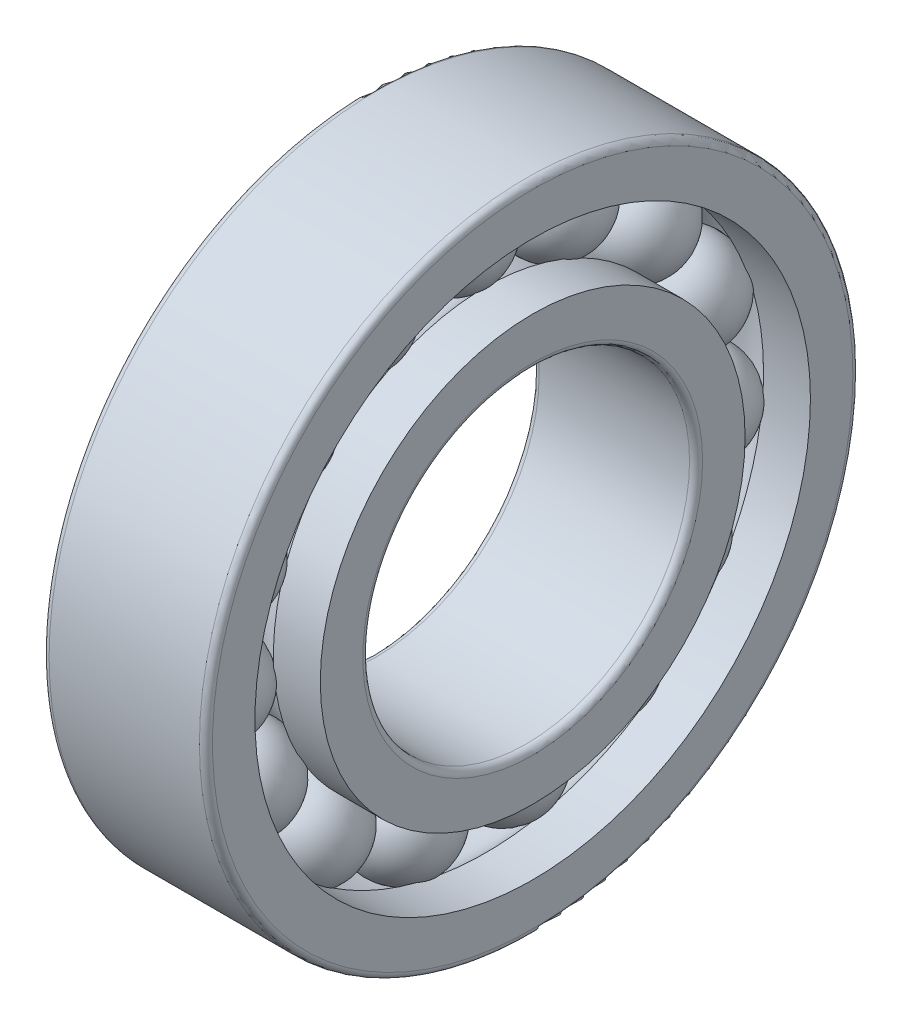
SolidWorks part; units mm, degrees
ref_plane "Plane1" through (0, 0, 0) normal (0, 0, 1) x (1, 0, 0)
ref_plane "Plane2" through (0, 0, 0) normal (0, 1, 0) x (1, 0, 0)
ref_plane "Plane3" through (0, 0, 0) normal (1, 0, 0) x (0, 0, -1)
other "Configuration Table"
sketch "Clipboard" plane through (0, 0, 0) normal (0, 0, 1) x (1, 0, 0)
  line L0 (-10, 0) -> (10, 0) construction
  line L1 (0, 0) -> (21.5988, -5.7874)
  line L2 (0, 0) -> (4.7618, -0.0831)
  line L3 (0, 0) -> (22.3573, 0.3902)
  line L4 (0, 0) -> (-22.3573, -0.3902)
sketch "CagSpiSke" plane through (0, 0, 0) normal (0, 0, 1) x (1, 0, 0)
  line L0 (0.0952, 4.6038) -> (0.0953, 4.9213)
  line L1 (0.0953, 4.9213) -> (-0.0953, 4.9213)
  line L2 (-0.0953, 4.9213) -> (-0.0952, 4.6038)
  line L3 (-0.0952, 4.6038) -> (0.0952, 4.6038)
  line L4 (-20.6375, 0) -> (20.6375, 0) construction
  line L5 (0, 0) -> (0, 23.7692) construction
revolve "CageSpine" add sketch "CagSpiSke" angle 0.001 about L4 reverse direction yes
ref_axis "Axis1" through (-50, 0, 0) along (1, 0, 0)
sketch "CagBalSke" plane through (0, 0, 0) normal (0, 0, 1) x (1, 0, 0)
  line L0 (-1.0478, 4.7625) -> (1.0478, 4.7625)
  line L1 (-1.905, 4.7625) -> (1.905, 4.7625) construction
  line L2 (-10, 0) -> (10, 0) construction
  line L3 (0, 0) -> (0, 24) construction
  arc A0 (1.0478, 4.7625) -> (-1.0478, 4.7625) centre (0, 4.7625) cw
revolve "CageBall" [suppressed] add sketch "CagBalSke" angle 360 about L1 reverse direction yes
pattern_circular "CageBalls" [suppressed] count 15 every 24 about axis through (-50, 0, 0) along (1, 0, 0)
sketch "CagTrmODSke" plane through (0, 0, 0) normal (0, 0, 1) x (1, 0, 0)
  line L0 (1.0488, 4.9212) -> (1.0488, 5.8113)
  line L1 (1.0488, 5.8113) -> (-1.0488, 5.8113)
  line L2 (-1.0488, 5.8113) -> (-1.0488, 4.9212)
  line L3 (-1.0488, 4.9212) -> (1.0488, 4.9212)
  line L4 (-20.6375, 0) -> (20.6375, 0) construction
  line L5 (0, 0) -> (0, 25) construction
revolve "CageTrimOD" [suppressed] cut sketch "CagTrmODSke" angle 360 about L4 reverse direction yes
sketch "CagTrmIDSke" plane through (0, 0, 0) normal (0, 0, 1) x (1, 0, 0)
  line L0 (1.0487, 3.7158) -> (1.0488, 4.6037)
  line L1 (1.0488, 4.6037) -> (-1.0488, 4.6037)
  line L2 (-1.0488, 4.6037) -> (-1.0487, 3.7158)
  line L3 (-1.0487, 3.7158) -> (1.0487, 3.7158)
  line L4 (-20.6375, 0) -> (20.6375, 0) construction
  line L5 (0, 0) -> (0, 25) construction
revolve "CageTrimID" [suppressed] cut sketch "CagTrmIDSke" angle 360 about L4 reverse direction yes
sketch "BalSimSke" plane through (0, 0, 0) normal (0, 0, 1) x (1, 0, 0)
  line L0 (-10, 0) -> (10, 0) construction
  line L1 (-10, 4.7625) -> (10, 4.7625) construction
  line L2 (0, 0) -> (0, 23) construction
  circle A0 centre (0, 4.7625) radius 0.9525
revolve "BallsSimplified" [suppressed] add sketch "BalSimSke" angle 360 about L0
sketch "BalDetSke" plane through (0, 0, 0) normal (0, 0, 1) x (1, 0, 0)
  line L0 (-0.9525, 4.7625) -> (0.9525, 4.7625)
  line L1 (-1.905, 4.7625) -> (1.905, 4.7625) construction
  line L2 (0, 0) -> (0, 25) construction
  arc A0 (0.9525, 4.7625) -> (-0.9525, 4.7625) centre (0, 4.7625) cw
revolve "BallDetailed" add sketch "BalDetSke" angle 360 about L1 reverse direction yes
sketch "InnRacSke" plane through (0, 0, 0) normal (0, 0, 1) x (1, 0, 0)
  line L0 (-0.676, 4.1275) -> (-1.5875, 4.1275)
  line L1 (-1.5875, 4.1275) -> (-1.5875, 3.302)
  line L2 (-1.4605, 3.175) -> (1.4605, 3.175)
  line L3 (1.5875, 3.302) -> (1.5875, 4.1275)
  line L4 (1.5875, 4.1275) -> (0.676, 4.1275)
  line L5 (-20.6375, 0) -> (20.6375, 0) construction
  line L6 (0, 0) -> (0, 30) construction
  arc A0 (-1.5875, 3.302) -> (-1.4605, 3.175) centre (-1.4605, 3.302) ccw
  arc A1 (1.4605, 3.175) -> (1.5875, 3.302) centre (1.4605, 3.302) ccw
  arc A2 (0.676, 4.1275) -> (-0.676, 4.1275) centre (0, 4.7625) cw
  dimension "OD" = 8.255
revolve "InnerRace" add sketch "InnRacSke" angle 360 about L5 reverse direction yes
sketch "OutRacSke" plane through (0, 0, 0) normal (0, 0, 1) x (1, 0, 0)
  line L0 (-0.676, 5.3975) -> (-1.5875, 5.3975)
  line L1 (-1.5875, 5.3975) -> (-1.5875, 6.223)
  line L2 (-1.4605, 6.35) -> (1.4605, 6.35)
  line L3 (1.5875, 6.223) -> (1.5875, 5.3975)
  line L4 (1.5875, 5.3975) -> (0.676, 5.3975)
  line L5 (-20.6375, 0) -> (20.6375, 0) construction
  line L6 (0, 0) -> (0, 30) construction
  arc A0 (-1.5875, 6.223) -> (-1.4605, 6.35) centre (-1.4605, 6.223) cw
  arc A1 (1.4605, 6.35) -> (1.5875, 6.223) centre (1.4605, 6.223) cw
  arc A2 (0.676, 5.3975) -> (-0.676, 5.3975) centre (0, 4.7625) ccw
revolve "OuterRace" add sketch "OutRacSke" angle 360 about L5 reverse direction yes
pattern_circular "BallsDetailed" count 15 every 24 about axis through (-50, 0, 0) along (1, 0, 0) of "BallDetailed"
equation "\"BallCLRad@Clipboard\" = ( \"OD@OutRacSke\" + \"ID@InnRacSke\" ) / 4"
equation "\"BallCLRad@BalSimSke\" = \"BallCLRad@Clipboard\""
equation "\"BallCLRad@BalDetSke\" = \"BallCLRad@Clipboard\""
equation "\"BallCLRad@InnRacSke\" = \"BallCLRad@Clipboard\""
equation "\"BallCLRad@OutRacSke\" = \"BallCLRad@Clipboard\""
equation "\"Ball_diameter@InnRacSke\" = \"Ball_diameter@BalDetSke\" - 0.05"
equation "\"Ball_diameter@OutRacSke\" = \"Ball_diameter@BalDetSke\" - 0.05"
equation "\"Ball_diameter@BalSimSke\" = \"Ball_diameter@BalDetSke\""
equation "\"Width@OutRacSke\" = \"Width@InnRacSke\""
equation "\"Fillet_radius@OutRacSke\" = \"Fillet_radius@InnRacSke\""
equation "\"Max_count@Clipboard\" = int( 3.14159265 / atn(( \"Ball_diameter@BalDetSke\" / 2) / sqr( \"BallCLRad@Clipboard\"  *  \"BallCLRad@Clipboard\" - ( \"Ball_diameter@BalDetSke\" / 2) *  ( \"Ball_diameter@BalDetSke\" / 2))))"
equation "\"Max_count@Clipboard\" = ((sgn( \"Max_count@Clipboard\" - \"Count@Clipboard\" )-1)*( \"Max_count@Clipboard\" - \"Count@Clipboard\" ))/-2+ \"Count@Clipboard\""
equation "\"Count@BallsDetailed\" = int( \"Show_count@Clipboard\" ) "
equation "\"Count@BallsDetailed\" = ((sgn( \"Count@BallsDetailed\" - \"Max_count@Clipboard\" )-1)*( \"Count@BallsDetailed\" - \"Max_count@Clipboard\" ))/-2+ \"Max_count@Clipboard\""
equation "\"Count@BallsDetailed\" = ((sgn( \"Count@BallsDetailed\" - \"Min_count@Clipboard\" )+1)*( \"Count@BallsDetailed\" - \"Min_count@Clipboard\"))/2 +\"Min_count@Clipboard\""
equation "\"Angle@BallsDetailed\" = 360.0 / \"Max_count@Clipboard\""
equation "\"BallCLRad@CagBalSke\" = \"BallCLRad@Clipboard\""
equation "\"Count@CageBalls\" = \"Count@BallsDetailed\""
equation "\"Angle@CageBalls\" = \"Angle@BallsDetailed\""
equation "\"Angle@CageSpine\" =  \"Angle@CageBalls\" * ( \"Count@CageBalls\" -1 + int( \"Count@CageBalls\" / \"Max_count@Clipboard\" ) )  + 0.001 -  int( \"Count@CageBalls\" / \"Max_count@Clipboard\" ) * 0.001"
equation "\"Angle@CageSpine\" =  \"Angle@CageSpine\" * int( \"Min_count@Clipboard\" / 2) + int(1 / \"Min_count@Clipboard\")  * 0.001"
equation "\"CageWallOD@CagBalSke\" =  \"Ball_diameter@BalDetSke\" * 1.1"
equation "\"Thickness@CagSpiSke\" =  \"Ball_diameter@BalDetSke\" * 0.1"
equation "\"OD@CagTrmODSke\" = \"BallCLRad@Clipboard\" * 2 + \"CageWallOD@CagBalSke\" + 0.002"
equation "\"ID@CagTrmODSke\" = \"BallCLRad@Clipboard\" * 2 + \"Ball_diameter@BalDetSke\" / 6"
equation "\"OD@CagTrmIDSke\" = \"BallCLRad@Clipboard\" * 2 - \"Ball_diameter@BalDetSke\" / 6"
equation "\"ID@CagTrmIDSke\" = \"BallCLRad@Clipboard\" * 2 - \"CageWallOD@CagBalSke\" + 0.002"
equation "\"OD@CagSpiSke\" = \"ID@CagTrmODSke\""
equation "\"ID@CagSpiSke\" = \"OD@CagTrmIDSke\""
equation "\"Width@CagTrmODSke\" = \"CageWallOD@CagBalSke\" + 0.002"
equation "\"Width@CagTrmIDSke\" = \"CageWallOD@CagBalSke\" + 0.002"
